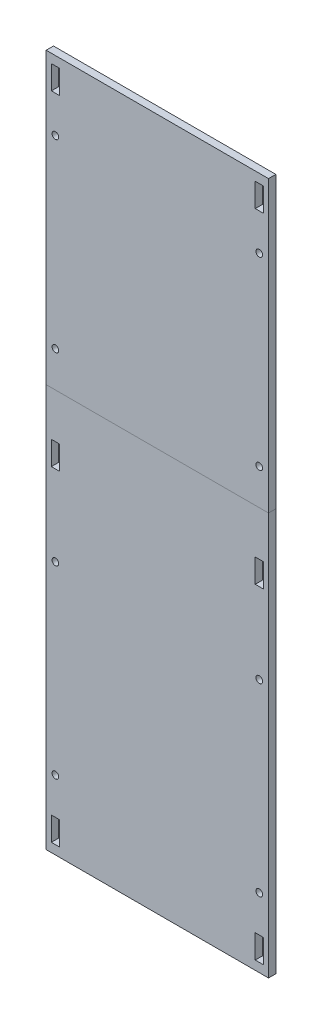
SolidWorks part; units mm, degrees
ref_plane "Front Plane" through (0, 0, 0) normal (0, 0, 1) x (1, 0, 0)
ref_plane "Top Plane" through (0, 0, 0) normal (0, 1, 0) x (1, 0, 0)
ref_plane "Right Plane" through (0, 0, 0) normal (1, 0, 0) x (0, 0, -1)
sketch "Sketch1" plane through (0, 0, 0) normal (0, 0, 1) x (1, 0, 0)
  line L2 (-44.17, -150) -> (-44.17, 150) construction
  line L4 (44.17, -150) -> (44.17, 150) construction
  line L5 (-44.17, -150) -> (44.17, 150) construction
  line L6 (-44.17, 150) -> (44.17, -150) construction
  line L7 (-48.17, -150) -> (48.17, -150)
  line L8 (-48.17, -150) -> (-48.17, 150)
  line L9 (-48.17, 150) -> (48.17, 150)
  line L10 (48.17, -150) -> (48.17, 150)
  line L11 (-48.17, -150) -> (48.17, 150) construction
  line L12 (-48.17, 150) -> (48.17, -150) construction
  line L13 (-45.9162, 135.875) -> (-42.4237, 135.875)
  line L14 (-45.9162, 135.875) -> (-45.9162, 146.125)
  line L15 (-45.9162, 146.125) -> (-42.4237, 146.125)
  line L16 (-42.4237, 135.875) -> (-42.4237, 146.125)
  line L17 (-45.9162, 135.875) -> (-42.4237, 146.125) construction
  line L18 (-45.9162, 146.125) -> (-42.4237, 135.875) construction
  line L19 (-45.9162, -5.125) -> (-42.4237, -5.125)
  line L20 (-45.9162, -5.125) -> (-45.9162, 5.125)
  line L21 (-45.9162, 5.125) -> (-42.4237, 5.125)
  line L22 (-42.4237, -5.125) -> (-42.4237, 5.125)
  line L23 (-45.9162, -5.125) -> (-42.4237, 5.125) construction
  line L24 (-45.9162, 5.125) -> (-42.4237, -5.125) construction
  line L25 (-45.9162, -146.125) -> (-42.4237, -146.125)
  line L26 (-45.9162, -146.125) -> (-45.9162, -135.875)
  line L27 (-45.9162, -135.875) -> (-42.4237, -135.875)
  line L28 (-42.4237, -146.125) -> (-42.4237, -135.875)
  line L29 (-45.9162, -146.125) -> (-42.4237, -135.875) construction
  line L30 (-45.9162, -135.875) -> (-42.4237, -146.125) construction
  circle A0 centre (-44.17, 120) radius 2.5 construction
  circle A1 centre (44.17, 120) radius 2.5 construction
  point P0 (0, 0)
  point P10 (-44.17, 141)
  point P12 (0, 0)
  point P20 (-44.17, 0)
  point P25 (-44.17, -141)
  dimension "D3" = 30
  dimension "D4" = 5
  dimension "D5" = 4
  dimension "D1" = 88.34
  dimension "D2" = 300
  dimension "D6" = 3.4925
  dimension "D7" = 10.25
  dimension "D8" = 9
  dimension "D9" = 9
extrude "Boss-Extrude1" add sketch "Sketch1" along normal mid plane 3.175 contours L9 L10 L7 L8
extrude "Cut-Extrude1" cut sketch "Sketch1<3>" against normal through all both and the other way through all contours L13 L16 L15 L14 | L19 L22 L21 L20 | L25 L28 L27 L26 region at (-44.17, 141, 0) region at (-44.17, 0, 0) region at (-44.17, -141, 0)
sketch "Sketch1<3>" plane through (0, 0, 0) normal (0, 0, 1) x (1, 0, 0) same geometry as "Sketch1"
hole_wizard "M2.5 Clearance Hole1" positions "Sketch2" profile "Sketch3" hole size "M2.5" standard "ANSI Metric" end condition through all
sketch "Sketch2" plane through (0, 0, 1.5875) normal (0, 0, 1) x (1, 0, 0)
  point P0 (-44.17, 120)
sketch "Sketch3" plane through (-44.17, 120, 1.5875) normal (1, 0, 0) x (0, -1, 0)
  line L0 (0, 0) -> (0, 3.175)
  line L1 (0, 3.175) -> (1.45, 3.175)
  line L2 (1.45, 3.175) -> (1.45, 0)
  line L5 (1.45, 0) -> (0, 0)
  line L11 (0, -6.35) -> (0, 107.95) construction
  dimension "Thru Hole Dia." = 2.9
  dimension "Thru Hole Depth" = 3.175
pattern_linear "LPattern1" count 4 spacing 80 along (0, -1, 0) of "M2.5 Clearance Hole1"
mirror "Mirror1" about plane through (0, 0, 0) normal (1, 0, 0) of "LPattern1", "Cut-Extrude1"
ref_plane "Plane1" through (0, 24.5, 0) normal (0, 1, 0) x (1, 0, 0)
split "Split1" trim tools "Plane1" bodies to split 105 resulting bodies 108 109
